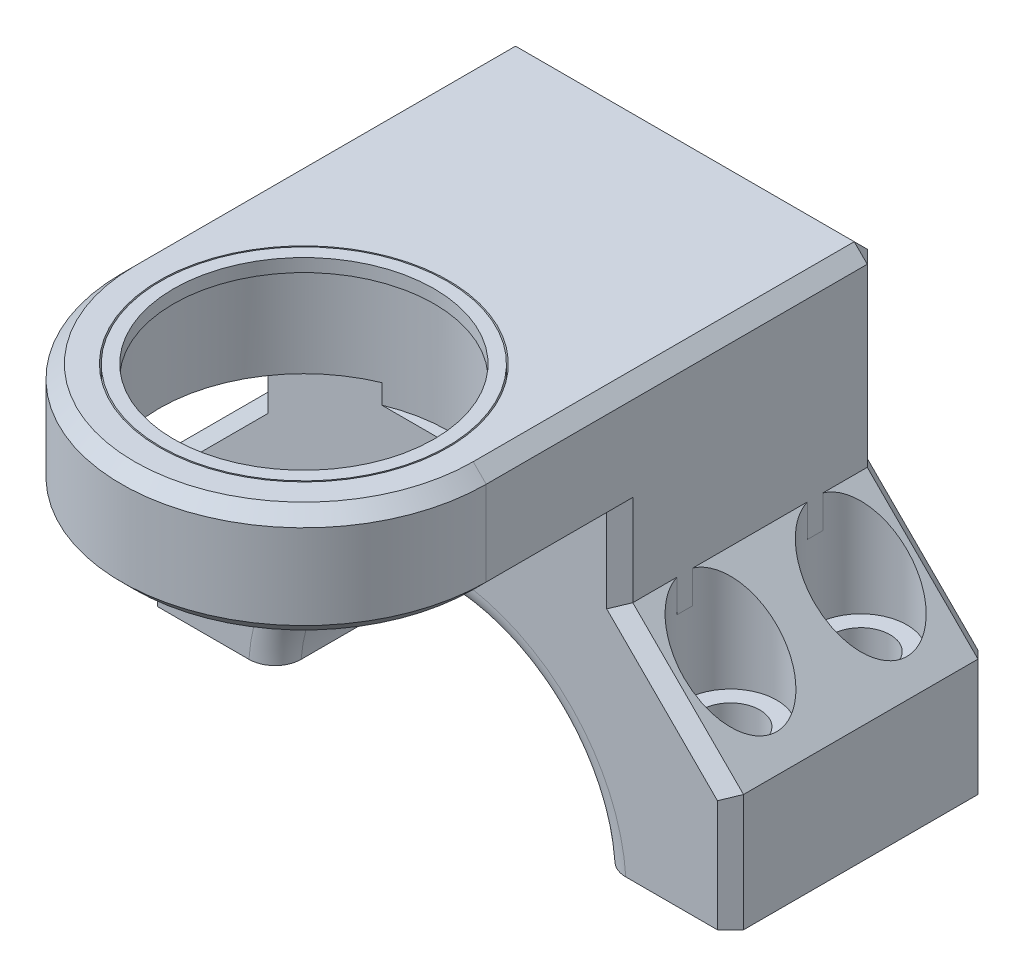
SolidWorks part; units mm, degrees
ref_plane "Front Plane" through (0, 0, 0) normal (0, 0, 1) x (1, 0, 0)
ref_plane "Top Plane" through (0, 0, 0) normal (0, 1, 0) x (1, 0, 0)
ref_plane "Right Plane" through (0, 0, 0) normal (1, 0, 0) x (0, 0, -1)
sketch "Sketch1" plane through (0, 0, 0) normal (0, 1, 0) x (1, 0, 0)
  line L0 (0, -10) -> (0, 10) construction
  line L1 (-22.5, 0) -> (22.5, 0) construction
  line L2 (0, 10) -> (-22.5, 10)
  line L3 (-22.5, 10) -> (-22.5, -10)
  line L4 (-22.5, -10) -> (22.5, -10)
  line L5 (22.5, -10) -> (22.5, 10)
  line L6 (22.5, 10) -> (0, 10)
  point P4 (0, 0)
  point P8 (0, 0)
  dimension "D1" = 45
  dimension "D2" = 20
extrude "Boss-Extrude1" add sketch "Sketch1" along normal blind 23
ref_plane "Plane1" through (0, 0, 10) normal (0, 0, 1) x (1, 0, 0)
sketch "Sketch2" plane through (0, 0, 10) normal (0, 0, 1) x (1, 0, 0)
  line L0 (-22.5, 0) -> (22.5, 0) construction
  line L1 (-12.5, 0) -> (-22.5, 0)
  line L2 (-22.5, 0) -> (-22.5, -2.5226)
  line L3 (-22.5, -2.5226) -> (22.5, -2.5226)
  line L4 (22.5, -2.5226) -> (22.5, 0)
  line L5 (22.5, 0) -> (12.5, 0)
  circle A0 centre (0, 0) radius 12.5 construction
  arc A1 (-12.5, 0) -> (12.5, 0) centre (0, 0) cw
  dimension "D1" = 25
extrude "Cut-Extrude1" cut sketch "Sketch2" against normal up to next
sketch "Sketch3" plane through (0, 0, 0) normal (0, 1, 0) x (1, 0, 0)
  line L0 (-12.5, 10) -> (-12.5, 0) construction
  line L1 (-12.5, -10) -> (-12.5, 10) construction
  line L2 (-12.5, 0) -> (-22.5, 0) construction
  line L3 (-22.5, 10) -> (-22.5, -10) construction
  line L4 (-17.5, 0) -> (-17.5, -5) construction
  line L5 (-17.5, 0) -> (-17.5, 5) construction
  circle A0 centre (-17.5, -5) radius 2.25
  circle A1 centre (-17.5, 5) radius 2.25
  dimension "D1" = 4.5
  dimension "D2" = 4.5
extrude "Cut-Extrude2" cut sketch "Sketch3" along normal up to next
mirror "Mirror1" about plane through (0, 0, 0) normal (1, 0, 0) of "Cut-Extrude2"
sketch "Sketch4" plane through (0, 0, 0) normal (0, 1, 0) x (1, 0, 0)
  circle A0 centre (-17.5, 5) radius 3.55
  circle A1 centre (-17.5, -5) radius 3.55
  dimension "D1" = 7.1
  dimension "D2" = 7.1
extrude "Cut-Extrude3" cut sketch "Sketch4" against normal blind 13 from offset 23
mirror "Mirror2" about plane through (0, 0, 0) normal (1, 0, 0) of "Cut-Extrude3"
fillet "Fillet1" radius 2 2 edges at (0, 12.5, -10) (0, 12.5, 10)
chamfer "Chamfer1" distance 13 2 edges at (22.5, 23, 0) (-22.5, 23, 0)
ref_plane "Plane2" through (0, 23, 0) normal (0, 1, 0) x (1, 0, 0)
sketch "Sketch6" plane through (0, 23, 0) normal (0, 1, 0) x (1, 0, 0)
  line L0 (-14, 0) -> (14, 0) construction
  line L1 (-14, -10) -> (-14, 10)
  line L2 (-22.5, 10) -> (-9.5, 10) construction
  line L3 (14, -10) -> (14, 10)
  line L4 (9.5, 10) -> (22.5, 10) construction
  line L5 (-14, 10) -> (14, 10)
  line L6 (0, 0) -> (0, -20.25) construction
  line L7 (-14, -10) -> (-14, -20.25)
  line L8 (14, -10) -> (14, -20.25)
  circle A0 centre (0, -20.25) radius 11.1
  circle A1 centre (0, -20.25) radius 14 construction
  arc A2 (14, -20.25) -> (-14, -20.25) centre (0, -20.25) cw
  point P5 (0, 0)
  point P13 (-14, 0)
  point P18 (14, 0)
  dimension "D2" = 22.2
  dimension "D1" = 28
  dimension "D3" = 20.25
extrude "Boss-Extrude2" add sketch "Sketch6" along normal blind 10 and the other way blind 7 contours A2 L8 L3 L5 L1 L7 A0
ref_plane "Plane3" through (114, 0, 0) normal (1, 0, 0) x (0, 0, -1)
sketch "Sketch7" plane through (114, 0, 0) normal (1, 0, 0) x (0, 0, -1)
  line L0 (-10, 16) -> (-10, 24.5)
  line L1 (-10, 24.5) -> (-34.25, 24.5)
  line L2 (-34.25, 33) -> (-34.25, 16) construction
  line L3 (-34.25, 24.5) -> (-34.25, 16)
  line L4 (-34.25, 16) -> (-10, 16)
  dimension "D1" = 8.5
extrude "Cut-Extrude4" cut sketch "Sketch7" against normal up to next from surface
ref_plane "Plane4" through (0, 43, 0) normal (0, 1, 0) x (1, 0, 0)
sketch "Sketch8" plane through (0, 43, 0) normal (0, 1, 0) x (1, 0, 0)
  circle A0 centre (0, -20.25) radius 11
extrude "Extrude-Thin1" add sketch "Sketch8" against normal blind 1 from surface at -10 thin starting at face at (0, 33, 8.625) thin type one direction reverse wall 1
chamfer "Chamfer2" distance 1 19 edges at (-22.5, 5, 10) (-18.25, 14.25, 10) (-14, 21.5, 10) (-14, 24.5, 15.125) (0, 24.5, 34.25) (14, 24.5, 15.125) (14, 21.5, 10) (18.25, 14.25, 10) (22.5, 5, 10) (-14, 33, 5.125) (0, 33, 34.25) (14, 33, 5.125) (22.5, 5, -10) (18.25, 14.25, -10) (14, 25.75, -10) (0, 33, -10) (-14, 25.75, -10) (-18.25, 14.25, -10) (-22.5, 5, -10)
sketch "Sketch9" plane through (0, 0, 0) normal (0, 0, 1) x (1, 0, 0)
  line L0 (-22.5, 0) -> (22.5, 0)
  line L1 (22.5, 0) -> (22.5, 1)
  line L2 (22.5, 10) -> (22.5, 0) construction
  line L3 (22.5, 1) -> (-22.5, 1)
  line L4 (-22.5, 0) -> (-22.5, 10) construction
  line L5 (-22.5, 1) -> (-22.5, 0)
  point P5 (0, 0)
  dimension "D1" = 1
extrude "Cut-Extrude5" cut sketch "Sketch9" against normal up to next (10 mm away) and the other way up to next (10 mm away)
